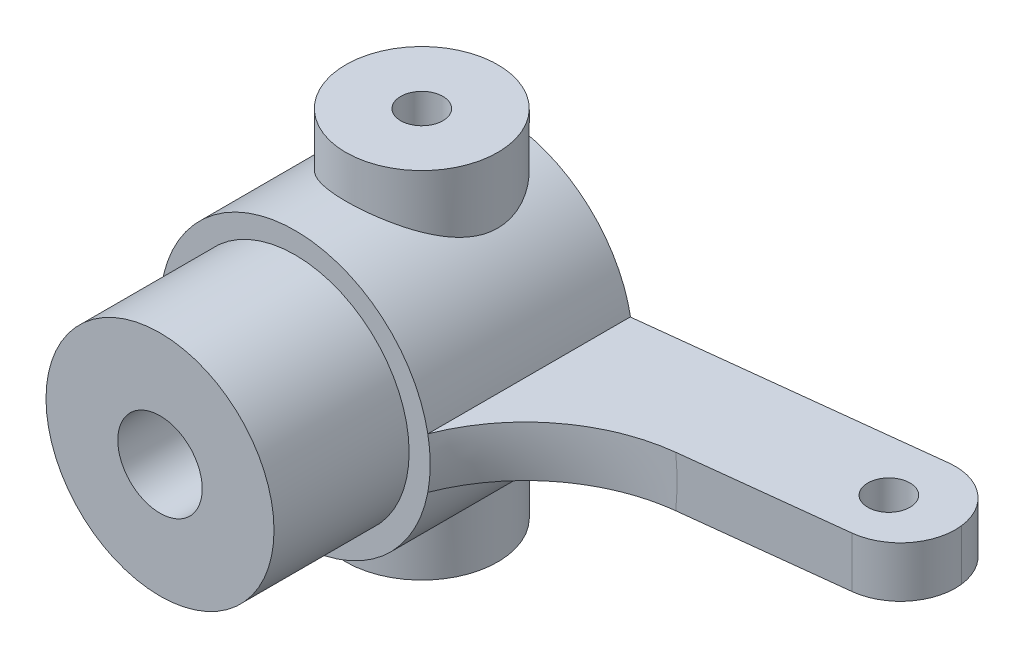
SolidWorks part; units mm, degrees
material "PBT General Purpose"
ref_plane "Front" through (0, 0, 0) normal (0, 0, 1) x (1, 0, 0)
ref_plane "Top" through (0, 0, 0) normal (0, 1, 0) x (1, 0, 0)
ref_plane "Right" through (0, 0, 0) normal (1, 0, 0) x (0, 0, -1)
sketch "Sketch1" plane through (0, 0, 0) normal (0, 0, 1) x (1, 0, 0)
  circle A0 centre (0, 0) radius 8
extrude "Boss-Extrude1" add sketch "Sketch1" along normal blind 12
sketch "Sketch2" plane through (0, 0, 12) normal (0, 0, 1) x (1, 0, 0)
  circle A0 centre (0, 0) radius 6.75
  dimension "D1" = 13.5
extrude "Boss-Extrude2" add sketch "Sketch2" along normal blind 8
sketch "Sketch3" plane through (0, 0, 0) normal (0, 0, -1) x (-1, 0, 0)
  circle A0 centre (0, 0) radius 6.25
  dimension "D1" = 12.5
sketch "Sketch4" plane through (0, 0, 20) normal (0, 0, 1) x (1, 0, 0)
  circle A0 centre (0, 0) radius 2.5
  dimension "D1" = 5
sketch "Sketch5" plane through (0, 0, 0) normal (0, 0, -1) x (-1, 0, 0)
  circle A0 centre (0, 0) radius 4
  dimension "D1" = 8
extrude "Cut-Extrude3" cut sketch "Sketch4" against normal through all contours A0
sketch "Sketch6" plane through (0, 0, 0) normal (1, 0, 0) x (0, 0, -1)
  line L1 (4.5, -8.9981) -> (-4.5, -8.9981)
  line L2 (4.5, -8.9981) -> (4.5, 8.9981)
  line L3 (4.5, 8.9981) -> (-4.5, 8.9981)
  line L4 (-4.5, -8.9981) -> (-4.5, 8.9981)
  line L5 (4.5, -8.9981) -> (-4.5, 8.9981) construction
  line L6 (4.5, 8.9981) -> (-4.5, -8.9981) construction
  point P0 (0, 0)
  dimension "D1" = 9
extrude "Cut-Extrude4" cut sketch "Sketch6" against normal blind 10
sketch "Sketch9" plane through (0, 0, 0) normal (0, 1, 0) x (1, 0, 0)
  line L0 (8, 0) -> (28, 0) construction
  line L1 (28, 0) -> (28, 2.3) construction
  line L2 (28, 2.3) -> (8, 0) construction
  line L3 (28, 2.3) -> (28.7426, -4.1574) construction
  dimension "D1" = 20
  dimension "D2" = 2.3
  dimension "D3" = 6.5
ref_plane "Plane3" through (27.8956, 0, -3.208) normal (-0.9935, 0, 0.1142) x (0.1142, 0, 0.9935)
sketch "Sketch10" plane through (27.8956, 0, -3.208) normal (-0.9935, 0, 0.1142) x (0.1142, 0, 0.9935)
  line L1 (0.914, 0) -> (7.414, 0)
  line L2 (0.914, 0) -> (0.914, 1.5)
  line L3 (0.914, 1.5) -> (7.414, 1.5)
  line L4 (7.414, 0) -> (7.414, 1.5)
  dimension "D1" = 6.5
  dimension "D2" = 1.5
sketch "Sketch11" plane through (27.8956, 0, -3.208) normal (-0.9935, 0, 0.1142) x (0.1142, 0, 0.9935)
  line L1 (0.914, 0) -> (7.414, 0)
  line L2 (0.914, 0) -> (0.914, -1.5)
  line L3 (0.914, -1.5) -> (7.414, -1.5)
  line L4 (7.414, 0) -> (7.414, -1.5)
  dimension "D1" = 1.5
extrude "Boss-Extrude3" add sketch "Sketch11" along normal up to surface (20.8793 mm away) up to face at (8, 0, 12)
extrude "Boss-Extrude4" add sketch "Sketch10" along normal up to surface (20.1318 mm away) up to face at (8, 0, 12)
fillet "Fillet1" radius 10 1 edges at (8, 0, 6.5428)
fillet "Fillet2" radius 3.25 2 edges at (28, 0, -2.3) (28.7426, 0, 4.1574)
sketch "Sketch12" plane through (0, -1.5, 0) normal (0, -1, 0) x (-1, 0, 0)
  circle A0 centre (-24.65, -1.4939) radius 1.25
  dimension "D1" = 2.5
extrude "Cut-Extrude6" cut sketch "Sketch12" against normal up to next
cosmetic thread "Cosmetic Thread1" parameters "D2"=3
cosmetic thread "Cosmetic Thread3" parameters "D2"=3
ref_plane "Plane5" through (0, 8, 0) normal (0, 1, 0) x (1, 0, 0)
sketch "Sketch13" plane through (0, 8, 0) normal (0, 1, 0) x (1, 0, 0)
  circle A0 centre (0, -4.5) radius 4.5
  dimension "D1" = 9
extrude "Boss-Extrude5" add sketch "Sketch13" along normal blind 2.5 and the other way blind 18.5
extrude "Cut-Extrude7" cut sketch "Sketch3" against normal blind 10 contours A0
sketch "Sketch14" plane through (0, 10.5, 0) normal (0, 1, 0) x (1, 0, 0)
  circle A0 centre (0, -4.5) radius 1.25
  dimension "D1" = 2.5
extrude "Cut-Extrude8" cut sketch "Sketch14" against normal blind 3.6 contours A0
cosmetic thread "Cosmetic Thread2" parameters "D2"=3
mirror "Mirror1" about plane through (0, 0, 0) normal (0, 1, 0) of "Cut-Extrude8"
extrude "Cut-Extrude9" cut sketch "Sketch5" against normal blind 13
